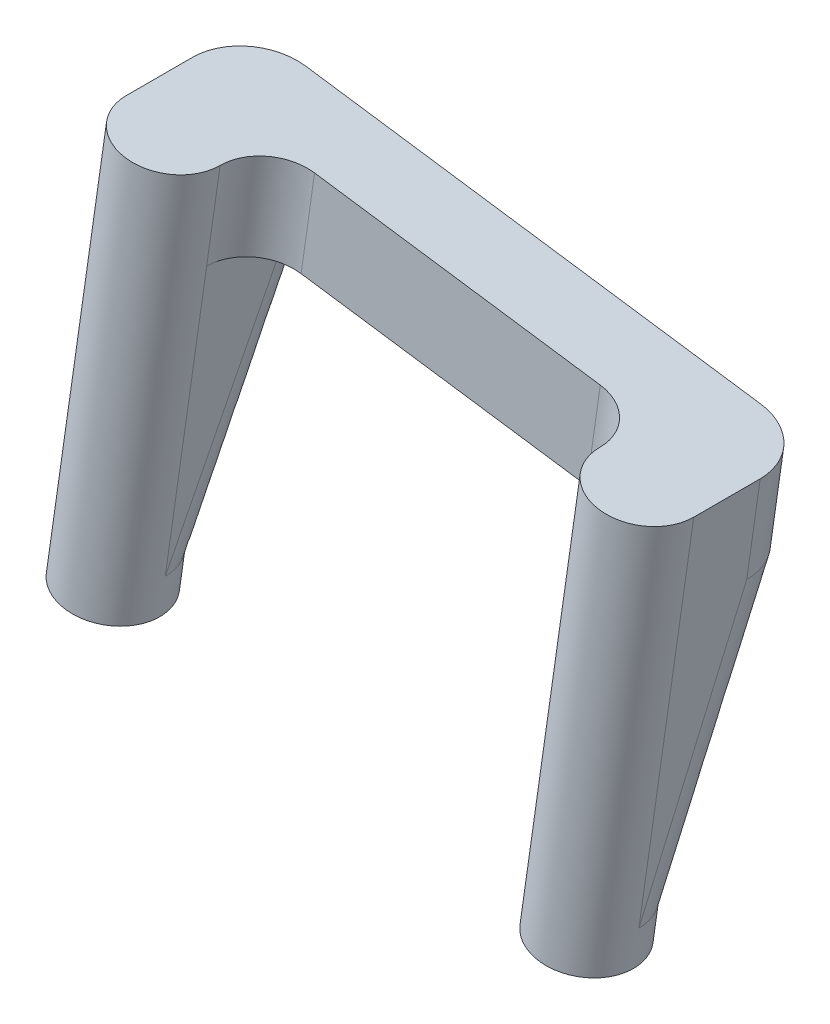
SolidWorks part; units mm, degrees
ref_plane "Спереди" through (0, 0, 0) normal (0, 0, 1) x (1, 0, 0)
ref_plane "Сверху" through (0, 0, 0) normal (0, 1, 0) x (1, 0, 0)
ref_plane "Справа" through (0, 0, 0) normal (1, 0, 0) x (0, 0, -1)
sketch "Sketch1" plane through (21.6709, 151.4259, 0) normal (0.1417, 0.9899, 0) x (0.9899, -0.1417, 0)
  circle A0 centre (75.9522, -57.0259) radius 0.85
  circle A1 centre (75.9522, -57.0259) radius 2.5
  circle A2 centre (50.7522, -57.0259) radius 0.85
  circle A3 centre (50.7522, -57.0259) radius 2.5
  dimension "D1" = 1.7
  dimension "D2" = 5
extrude "Boss-Extrude1" add sketch "Sketch1" along normal blind 8
sketch "Sketch2" plane through (22.8042, 159.3453, 0) normal (0.1417, 0.9899, 0) x (0.9899, -0.1417, 0)
  circle A0 centre (75.9522, -57.0259) radius 2.5 construction
  circle A1 centre (50.7522, -57.0259) radius 2.5 construction
  circle A2 centre (75.9522, -57.0259) radius 2.5
  circle A3 centre (50.7522, -57.0259) radius 2.5
extrude "Boss-Extrude2" add sketch "Sketch2" along normal up to surface (14.4 mm away)
sketch "Sketch3" plane through (24.8442, 173.6, 0) normal (0.1417, 0.9899, 0) x (0.9899, -0.1417, 0)
  line L0 (55.7522, -54.5259) -> (70.9522, -54.5259)
  line L1 (48.2522, -57.0259) -> (53.2522, -57.0259)
  line L2 (48.2522, -57.0259) -> (48.2522, -53.5259)
  line L3 (51.2522, -50.5259) -> (75.4522, -50.5259)
  line L4 (78.4522, -57.0259) -> (78.4522, -53.5259)
  line L5 (73.4522, -57.0259) -> (78.4522, -57.0259)
  circle A0 centre (50.7522, -57.0259) radius 2.5 construction
  circle A1 centre (75.9522, -57.0259) radius 2.5 construction
  arc A2 (48.2522, -57.0259) -> (53.2522, -57.0259) centre (50.7522, -57.0259) ccw
  arc A3 (73.4522, -57.0259) -> (78.4522, -57.0259) centre (75.9522, -57.0259) ccw
  arc A4 (55.7522, -54.5259) -> (53.2522, -57.0259) centre (55.7522, -57.0259) ccw
  arc A5 (73.4522, -57.0259) -> (70.9522, -54.5259) centre (70.9522, -57.0259) ccw
  arc A6 (75.4522, -50.5259) -> (78.4522, -53.5259) centre (75.4522, -53.5259) cw
  arc A7 (48.2522, -53.5259) -> (51.2522, -50.5259) centre (51.2522, -53.5259) cw
  circle M5 centre (75.9522, -57.0259) radius 2.5
  dimension "D2" = 3
  dimension "D1" = 4
extrude "Boss-Extrude3" add sketch "Sketch3" against normal blind 5 contours A7 L2 L1 A4 L0 A5 L4 A6 L3 M5 region at (86.6491, 164.755, 52.9672)
sketch "Sketch4" plane through (24.1359, 168.6505, 0) normal (-0.1417, -0.9899, 0) x (0.9899, -0.1417, 0)
  line L0 (53.2522, 57.0259) -> (53.2522, 52.5259)
  line L1 (73.4522, 57.0259) -> (73.4522, 52.5259)
  line L4 (48.2522, 57.0259) -> (48.2522, 53.5259)
  line L5 (51.2522, 50.5259) -> (75.4522, 50.5259)
  line L6 (78.4522, 53.5259) -> (78.4522, 57.0259)
  line L7 (70.9522, 54.5259) -> (55.7522, 54.5259)
  line L8 (48.2522, 57.0259) -> (48.2522, 53.5259)
  line L10 (78.4522, 53.5259) -> (78.4522, 57.0259)
  arc A0 (51.2522, 50.5259) -> (53.2522, 52.5259) centre (51.2522, 52.5259) ccw
  arc A1 (73.4522, 52.5259) -> (75.4522, 50.5259) centre (75.4522, 52.5259) ccw
  arc A6 (48.2522, 57.0259) -> (53.2522, 57.0259) centre (50.7522, 57.0259) ccw
  arc A7 (48.2522, 53.5259) -> (51.2522, 50.5259) centre (51.2522, 53.5259) ccw
  arc A8 (75.4522, 50.5259) -> (78.4522, 53.5259) centre (75.4522, 53.5259) ccw
  arc A9 (73.4522, 57.0259) -> (78.4522, 57.0259) centre (75.9522, 57.0259) ccw
  arc A10 (70.9522, 54.5259) -> (73.4522, 57.0259) centre (70.9522, 57.0259) ccw
  arc A11 (53.2522, 57.0259) -> (55.7522, 54.5259) centre (55.7522, 57.0259) ccw
  arc A12 (48.2522, 57.0259) -> (53.2522, 57.0259) centre (50.7522, 57.0259) ccw
  arc A13 (48.2522, 53.5259) -> (51.2522, 50.5259) centre (51.2522, 53.5259) ccw
  arc A14 (75.4522, 50.5259) -> (78.4522, 53.5259) centre (75.4522, 53.5259) ccw
  arc A15 (73.4522, 57.0259) -> (78.4522, 57.0259) centre (75.9522, 57.0259) ccw
  dimension "D1" = 0
extrude "Boss-Extrude4" add sketch "Sketch4" along normal offset from surface (15.4 mm away) 2 up to face at (69.4364, 144.5901, 57.0259)
sketch "Sketch8" plane through (24.1359, 168.6505, 0) normal (-0.1417, -0.9899, 0) x (0.9899, -0.1417, 0)
  line L4 (48.2522, 53.5259) -> (45.2522, 53.5259)
  line L5 (53.2522, 52.5259) -> (56.2522, 52.5259)
  line L6 (73.4522, 52.5259) -> (70.4522, 52.5259)
  line L7 (78.4522, 53.5259) -> (81.4522, 53.5259)
  arc A1 (48.2522, 53.5259) -> (51.2522, 50.5259) centre (51.2522, 53.5259) ccw construction
  arc A5 (51.2522, 50.5259) -> (53.2522, 52.5259) centre (51.2522, 52.5259) ccw construction
  arc A6 (73.4522, 52.5259) -> (75.4522, 50.5259) centre (75.4522, 52.5259) ccw construction
  arc A7 (75.4522, 50.5259) -> (78.4522, 53.5259) centre (75.4522, 53.5259) ccw construction
  arc A8 (48.2522, 53.5259) -> (51.2522, 50.5259) centre (51.2522, 53.5259) ccw
  arc A9 (51.2522, 50.5259) -> (53.2522, 52.5259) centre (51.2522, 52.5259) ccw
  arc A10 (73.4522, 52.5259) -> (75.4522, 50.5259) centre (75.4522, 52.5259) ccw
  arc A11 (75.4522, 50.5259) -> (78.4522, 53.5259) centre (75.4522, 53.5259) ccw
  arc A12 (45.2522, 53.5259) -> (51.2522, 47.5259) centre (51.2522, 53.5259) ccw
  arc A13 (51.2522, 47.5259) -> (56.2522, 52.5259) centre (51.2522, 52.5259) ccw
  arc A14 (70.4522, 52.5259) -> (75.4522, 47.5259) centre (75.4522, 52.5259) ccw
  arc A15 (75.4522, 47.5259) -> (81.4522, 53.5259) centre (75.4522, 53.5259) ccw
  dimension "D1" = 3
sketch "Sketch9" plane through (21.9542, 153.4058, 0) normal (-0.1417, -0.9899, 0) x (0.9899, -0.1417, 0)
  line L0 (78.4522, 57.0259) -> (78.4522, 53.5259) construction
  line L1 (48.2522, 57.0259) -> (43.2522, 57.0259)
  line L2 (53.2522, 57.0259) -> (58.2522, 57.0259)
  line L3 (73.4522, 57.0259) -> (68.4522, 57.0259)
  line L4 (78.4522, 57.0259) -> (83.4522, 57.0259)
  arc A0 (48.2522, 57.0259) -> (50.7522, 54.5259) centre (50.7522, 57.0259) ccw
  arc A1 (73.4522, 57.0259) -> (75.9522, 54.5259) centre (75.9522, 57.0259) ccw
  arc A2 (48.2522, 57.0259) -> (53.2522, 57.0259) centre (50.7522, 57.0259) ccw construction
  arc A3 (50.7522, 54.5259) -> (53.2522, 57.0259) centre (50.7522, 57.0259) ccw
  arc A4 (75.9522, 54.5259) -> (78.4522, 57.0259) centre (75.9522, 57.0259) ccw
  circle A5 centre (75.9522, 57.0259) radius 2.5 construction
  arc A6 (43.2522, 57.0259) -> (50.7522, 49.5259) centre (50.7522, 57.0259) ccw
  arc A7 (50.7522, 49.5259) -> (58.2522, 57.0259) centre (50.7522, 57.0259) ccw
  arc A8 (68.4522, 57.0259) -> (75.9522, 49.5259) centre (75.9522, 57.0259) ccw
  arc A9 (75.9522, 49.5259) -> (83.4522, 57.0259) centre (75.9522, 57.0259) ccw
  dimension "D1" = 5
loft "Cut-Loft7" cut section "Sketch9" section "Sketch8" connector at (64.7702, 147.2783, 57.0259) connector at (68.9317, 162.2396, 53.5259)
loft "Cut-Loft8" cut section "Sketch9<3>" section "Sketch8<8>" connector at (89.716, 143.7083, 57.0259) connector at (93.8775, 158.6696, 52.5259)
sketch "Sketch9<3>" plane through (21.9542, 153.4058, 0) normal (-0.1417, -0.9899, 0) x (0.9899, -0.1417, 0) same geometry as "Sketch9"
sketch "Sketch8<8>" plane through (24.1359, 168.6505, 0) normal (-0.1417, -0.9899, 0) x (0.9899, -0.1417, 0) same geometry as "Sketch8"
